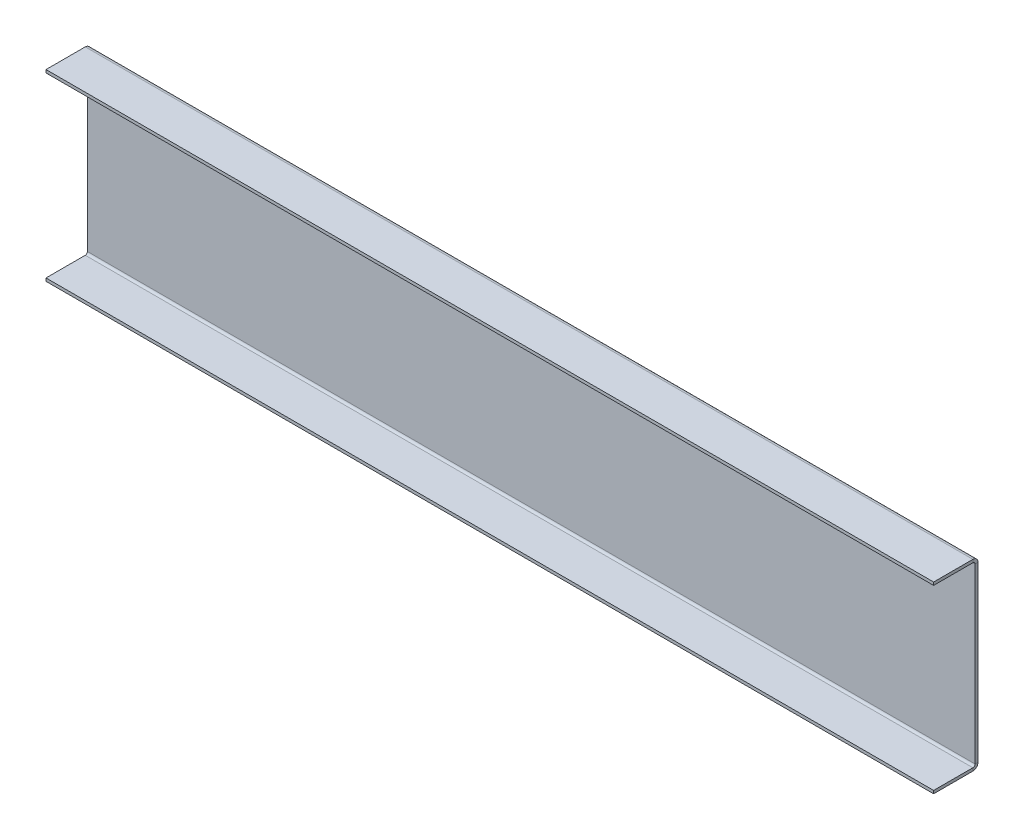
SolidWorks part; units mm, degrees
note: The reader was unsure of these and kept them because the rebuilt part matched: thickness of "Base-Flange1", "Edge-Flange1", "Sheet-Metal1", "Sheet-Metal2"; flange length of "Edge-Flange1".
ref_plane "Front Plane" through (0, 0, 0) normal (0, 0, 1) x (1, 0, 0)
ref_plane "Top Plane" through (0, 0, 0) normal (0, 1, 0) x (1, 0, 0)
ref_plane "Right Plane" through (0, 0, 0) normal (1, 0, 0) x (0, 0, -1)
sketch "Sketch1" plane through (0, 0, 0) normal (0, 0, 1) x (1, 0, 0)
  line L1 (-150, 30) -> (150, 30)
  line L2 (-150, 30) -> (-150, -30)
  line L3 (-150, -30) -> (150, -30)
  line L4 (150, 30) -> (150, -30)
  line L5 (-150, 30) -> (150, -30) construction
  line L6 (-150, -30) -> (150, 30) construction
  point P0 (0, 0)
  dimension "D1" = 300
  dimension "D2" = 60
base flange "Base-Flange1" sketch "Sketch1" thickness 1 reverse thickness direction no parameters "D1"=0.7366
edge flange "Edge-Flange1" sketch "Sketch10" flange profiles "Sketch10", "Sketch11" flange angle 90 flange length 15 flange position material outside bend radius 0.7366 thickness 1 relief rectangular parameters "D6"=10, "D8"=1
sketch "Sketch10" plane through (0, 30, 0) normal (0, 1, 0) x (-1, 0, 0)
  line L0 (-150, 0) -> (150, 0) construction
  line L1 (-150, 0) -> (150, 0)
  line L2 (-150, 0) -> (-150, 14)
  line L3 (-150, 14) -> (150, 14)
  line L4 (150, 14) -> (150, 0)
sketch "Sketch11" plane through (0, -30, 0) normal (0, -1, 0) x (1, 0, 0)
  line L0 (-150, 0) -> (150, 0) construction
  line L1 (-150, 0) -> (150, 0)
  line L2 (-150, 0) -> (-150, 14)
  line L3 (-150, 14) -> (150, 14)
  line L4 (150, 14) -> (150, 0)
bend "EdgeBend1" bend radius 0.7366 bend angle 90 parameters "D5"=1
bend "EdgeBend2" bend radius 0.7366 bend angle 90 parameters "D5"=2
sketch "Bend-Lines1" [suppressed] plane through (0, 0, 0) normal (0, 1, 0) x (1, 0, 0)
sketch "Bounding-Box1" [suppressed] plane through (0, 0, 0) normal (0, 1, 0) x (1, 0, 0)
sheet metal parameters "Sheet-Metal1" thickness 1 parameters "D1"=0.7366
flat pattern "Flat-Pattern1" [suppressed]
sketch "Bend-Lines2" plane through (0, 0, 0) normal (0, 1, 0) x (1, 0, 0)
sketch3d "Bounding-Box2" [suppressed]
  line L0 (150, -30, 0) -> (-150, -30, 0) construction
  line L1 (150, 30, 0) -> (-150, 30, 0) construction
  line L2 (150, -30, 0) -> (150, 30, 0) construction
  line L3 (-150, -30, 0) -> (-150, 30, 0) construction
sheet metal parameters "Sheet-Metal2" thickness 1 parameters "D1"=0.7366, "D7"=2
flat pattern "Flat-Pattern1"
sketch "Bend-Lines2" plane through (0, 0, 0) normal (0, 0, 1) x (1, 0, 0)
  line L0 (-150, -30.2346) -> (150, -30.2346) construction
  line L1 (150, 30.2346) -> (-150, 30.2346) construction
  line L2 (-150, -30.2346) -> (150, -30.2346) construction
  line L3 (150, 30.2346) -> (-150, 30.2346) construction
sketch3d "Bounding-Box2" [suppressed]
  line L0 (-150, -44.4692, 0) -> (150, -44.4692, 0) construction
  line L1 (-150, 44.4692, 0) -> (150, 44.4692, 0) construction
  line L2 (-150, -44.4692, 0) -> (-150, 44.4692, 0) construction
  line L3 (150, -44.4692, 0) -> (150, 44.4692, 0) construction
bend of the flat pattern "Flatten-<EdgeBend1>1"
bend of the flat pattern "Flatten-<EdgeBend2>1"
